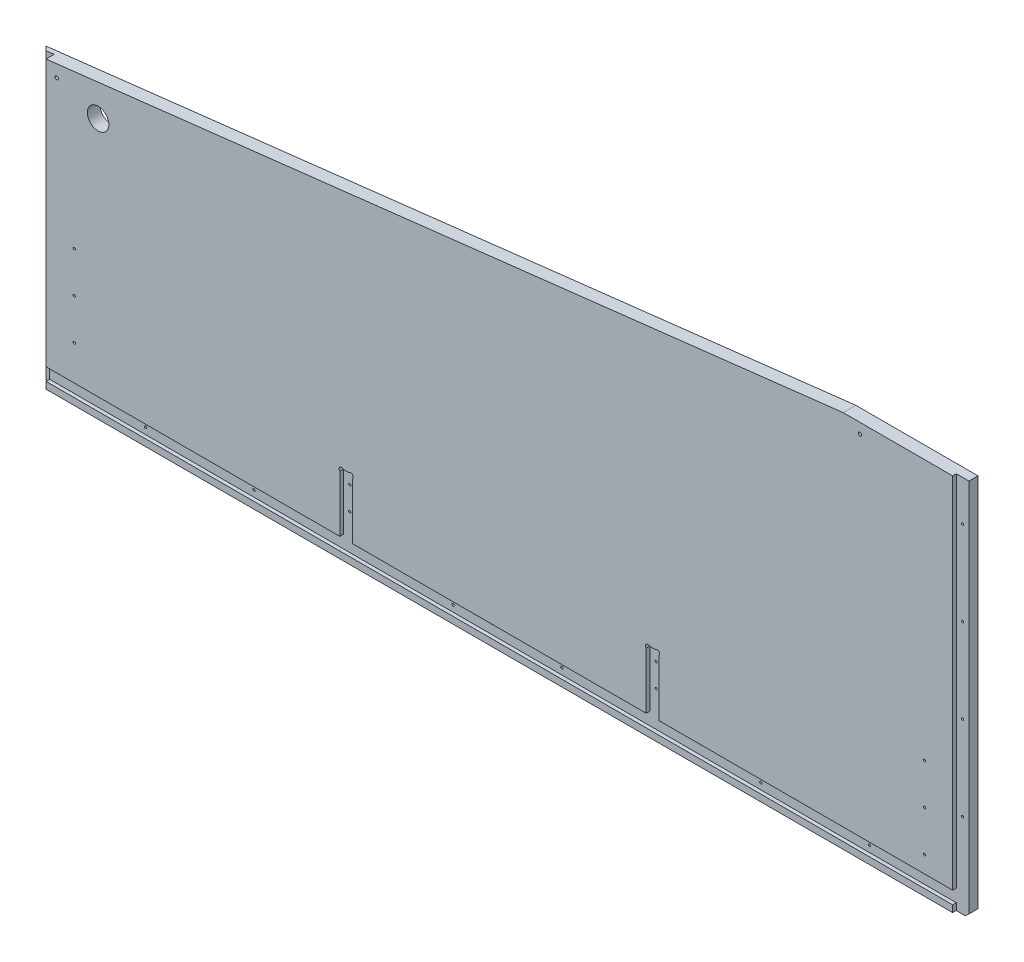
SolidWorks part; units mm, degrees
material "Pine"
ref_plane "Front Plane" through (0, 0, 0) normal (0, 0, 1) x (1, 0, 0)
ref_plane "Top Plane" through (0, 0, 0) normal (0, 1, 0) x (1, 0, 0)
ref_plane "Right Plane" through (0, 0, 0) normal (1, 0, 0) x (0, 0, -1)
sketch "Sketch1" plane through (0, 0, 0) normal (0, 0, 1) x (1, 0, 0)
  line L0 (8932.6508, -5243.5125) -> (10226.1458, -5243.5125)
  line L1 (9086.3208, -4722.0918) -> (10222.9708, -4853.7812)
  line L2 (8914.8708, -6342.0625) -> (10197.5708, -6342.0625)
  line L3 (8914.8708, -5808.6625) -> (10197.5708, -5808.6625)
  line L4 (8919.6333, -5253.0375) -> (10218.2083, -5253.0375)
  line L5 (9134.2633, -4656.1375) -> (9134.2633, -4638.3575)
  line L6 (9091.0833, -4638.3575) -> (9134.2633, -4638.3575)
  line L7 (9091.0833, -4567.2375) -> (9091.0833, -4638.3575)
  line L8 (9134.2633, -4656.1375) -> (9581.3033, -4656.1375)
  line L9 (9091.0833, -4567.2375) -> (9624.4833, -4567.2375)
  line L10 (9581.3033, -4656.1375) -> (9581.3033, -4638.3575)
  line L11 (9581.3033, -4638.3575) -> (9624.4833, -4638.3575)
  line L12 (9624.4833, -4567.2375) -> (9624.4833, -4638.3575)
  line L13 (8932.6508, -5225.7325) -> (9344.9775, -5225.7325)
  line L14 (8932.6508, -5256.2125) -> (8932.6508, -5243.5125)
  line L15 (8911.6958, -5256.2125) -> (8932.6508, -5256.2125)
  line L16 (8914.8708, -4722.0918) -> (9086.3208, -4722.0918)
  line L17 (8911.6958, -4715.5913) -> (8932.6508, -4715.5913)
  line L18 (8914.8708, -6342.0625) -> (8914.8708, -5808.6625)
  line L19 (12082.9917, -4722.0918) -> (10946.3417, -4853.7812)
  line L20 (12236.6617, -5243.5125) -> (10943.1667, -5243.5125)
  line L21 (10951.1042, -5253.0375) -> (12249.6792, -5253.0375)
  line L22 (10838.3917, -5656.2625) -> (11308.2917, -5656.2625)
  line L23 (10838.3917, -5719.7625) -> (11308.2917, -5719.7625)
  line L24 (10838.3917, -5742.5368) -> (11308.2917, -5742.5368)
  line L25 (10806.6417, -6342.0625) -> (11340.0417, -6342.0625)
  line L26 (10803.4667, -6335.7125) -> (11343.2167, -6335.7125)
  line L27 (10803.4667, -6317.9325) -> (11343.2167, -6317.9325)
  line L28 (10943.1667, -5225.7325) -> (11376.4483, -5225.7325)
  line L29 (11506.7292, -4754.5625) -> (10806.6417, -4827.5875)
  line L30 (11506.7292, -4567.2375) -> (11506.7292, -4754.5625)
  line L31 (10806.6417, -4567.2375) -> (10806.6417, -4827.5875)
  line L32 (10806.6417, -4567.2375) -> (11506.7292, -4567.2375)
  line L33 (10235.6708, -6329.3625) -> (10245.1958, -6329.3625)
  line L34 (10245.1958, -6329.3625) -> (10254.7208, -6278.5625)
  line L35 (10302.3458, -6329.3625) -> (10311.8708, -6278.5625)
  line L36 (10302.3458, -6329.3625) -> (10292.8208, -6329.3625)
  line L37 (10245.1958, -5821.3625) -> (10254.7208, -5872.1625)
  line L38 (10235.6708, -5821.3625) -> (10245.1958, -5821.3625)
  line L39 (10292.8208, -5821.3625) -> (10302.3458, -5821.3625)
  line L40 (10302.3458, -5821.3625) -> (10311.8708, -5872.1625)
  line L41 (10235.6708, -5821.3625) -> (10235.6708, -6329.3625)
  line L42 (10254.7208, -5872.1625) -> (10254.7208, -6278.5625)
  line L43 (10311.8708, -5872.1625) -> (10311.8708, -6278.5625)
  line L44 (10292.8208, -5821.3625) -> (10292.8208, -6329.3625)
  line L45 (8932.6508, -5225.7325) -> (8932.6508, -4715.5913)
  line L46 (8911.6958, -4715.5913) -> (8911.6958, -5256.2125)
  line L47 (8914.8708, -5248.275) -> (8914.8708, -4722.0918)
  line L48 (8919.6333, -5253.0375) -> (8914.8708, -5248.275)
  line L49 (8914.8708, -5145.0875) -> (8937.426, -5145.0875)
  line L50 (8914.8708, -5202.2375) -> (8937.426, -5202.2375)
  line L51 (10838.3917, -5656.2625) -> (10838.3917, -5719.7625)
  line L52 (10832.0417, -5736.1868) -> (10856.1717, -5736.1868)
  line L53 (10806.6417, -6342.0625) -> (10806.6417, -5818.7368)
  line L54 (10832.0417, -5649.9125) -> (10856.1717, -5649.9125)
  line L55 (10832.0417, -5726.1125) -> (10856.1717, -5726.1125)
  line L56 (10806.6417, -5818.7368) -> (10833.9015, -5818.7368)
  line L57 (10832.0417, -5806.0442) -> (10851.6815, -5806.0442)
  line L58 (10856.1717, -5801.5541) -> (10856.1717, -5736.1868)
  line L59 (10838.3917, -5814.2467) -> (10838.3917, -5742.5368)
  line L60 (10832.0417, -5806.0442) -> (10832.0417, -5736.1868)
  line L61 (10803.4667, -6317.9325) -> (10803.4667, -6335.7125)
  line L62 (10197.5708, -5808.6625) -> (10197.5708, -6342.0625)
  line L63 (9762.3842, -6348.4125) -> (9762.3842, -5802.3125)
  line L64 (9780.1642, -6348.4125) -> (9762.3842, -6348.4125)
  line L65 (9780.1642, -5802.3125) -> (9780.1642, -6348.4125)
  line L66 (9762.3842, -5802.3125) -> (9780.1642, -5802.3125)
  line L67 (9332.2775, -6348.4125) -> (9332.2775, -5802.3125)
  line L68 (9332.2775, -6348.4125) -> (9350.0575, -6348.4125)
  line L69 (9350.0575, -5802.3125) -> (9350.0575, -6348.4125)
  line L70 (9332.2775, -5802.3125) -> (9350.0575, -5802.3125)
  line L71 (9993.8374, -6061.075) -> (9993.8374, -6045.2418)
  line L72 (9998.5999, -6065.8375) -> (10014.4331, -6065.8375)
  line L73 (9998.5999, -6084.8875) -> (10014.4331, -6084.8875)
  line L74 (9993.8374, -6105.4832) -> (9993.8374, -6089.65)
  line L75 (9974.7874, -6105.4832) -> (9974.7874, -6089.65)
  line L76 (9954.1917, -6084.8875) -> (9970.0249, -6084.8875)
  line L77 (9974.7874, -6061.075) -> (9974.7874, -6045.2418)
  line L78 (9954.1917, -6065.8375) -> (9970.0249, -6065.8375)
  line L79 (10793.9417, -6237.2875) -> (10816.4969, -6237.2875)
  line L80 (10793.9417, -6294.4375) -> (10816.4969, -6294.4375)
  line L81 (10856.1717, -5649.9125) -> (10856.1717, -5726.1125)
  line L82 (10832.0417, -5726.1125) -> (10832.0417, -5649.9125)
  line L83 (10226.1458, -5225.7325) -> (10226.1458, -5243.5125)
  line L84 (10205.1908, -5257.8) -> (10205.1908, -4844.2499)
  line L85 (10230.9083, -4844.2499) -> (10230.9083, -5257.8)
  line L86 (10205.1908, -5257.8) -> (10230.9083, -5257.8)
  line L87 (10205.1908, -4844.2499) -> (10230.9083, -4844.2499)
  line L88 (10946.3417, -5176.8375) -> (10968.8969, -5176.8375)
  line L89 (9349.4676, -5141.9125) -> (9358.2674, -5141.9125)
  line L90 (10946.3417, -5119.6875) -> (10968.8969, -5119.6875)
  line L91 (9929.011, -4660.9635) -> (10066.0807, -4660.9635)
  line L92 (9929.011, -4678.7435) -> (10066.0807, -4678.7435)
  line L93 (10943.1667, -5225.7325) -> (10943.1667, -5243.5125)
  line L94 (10946.3417, -5248.275) -> (10951.1042, -5253.0375)
  line L95 (10946.3417, -5257.8063) -> (10946.3417, -4849.0188)
  line L96 (10964.1217, -5257.8) -> (10964.1217, -4844.2499)
  line L97 (10938.4042, -4844.2499) -> (10938.4042, -5257.8)
  line L98 (10938.4042, -5257.8) -> (10964.1217, -5257.8)
  line L99 (10964.1217, -4844.2499) -> (10938.4042, -4844.2499)
  line L100 (10344.8908, -4560.8875) -> (10369.0208, -4560.8875)
  line L101 (10344.8908, -4560.8875) -> (10369.0208, -4560.8875)
  line L102 (10800.2917, -4560.8875) -> (10824.4217, -4560.8875)
  line L103 (10200.4156, -5119.6875) -> (10222.9708, -5119.6875)
  line L104 (10200.4156, -5176.8375) -> (10222.9708, -5176.8375)
  line L105 (9344.9775, -5146.4026) -> (9344.9775, -5225.7325)
  line L106 (10344.8908, -4560.8875) -> (10344.8908, -4833.9375)
  line L107 (9792.8642, -5225.7325) -> (9792.8642, -5146.4026)
  line L108 (9362.7575, -5225.7325) -> (9775.0842, -5225.7325)
  line L109 (9680.3633, -4761.8396) -> (9680.3633, -4559.9604)
  line L110 (9656.2333, -4559.9604) -> (9680.3633, -4559.9604)
  line L111 (9656.2333, -4761.8396) -> (9680.3633, -4761.8396)
  line L112 (9656.2333, -4761.8396) -> (9656.2333, -4559.9604)
  line L113 (9779.5743, -5141.9125) -> (9788.374, -5141.9125)
  line L114 (10070.5708, -4665.4536) -> (10070.5708, -4674.2534)
  line L115 (9924.5208, -4674.2534) -> (9924.5208, -4665.4536)
  line L116 (12127.4417, -6188.3925) -> (12205.5015, -6188.3925)
  line L117 (12209.9917, -6170.6125) -> (12209.9917, -6183.9024)
  line L118 (9792.8642, -5225.7325) -> (10226.1458, -5225.7325)
  line L119 (9662.5833, -4754.5625) -> (10362.6708, -4827.5875)
  line L120 (9662.5833, -4567.2375) -> (9662.5833, -4754.5625)
  line L121 (10362.6708, -4567.2375) -> (10362.6708, -4827.5875)
  line L122 (9662.5833, -4567.2375) -> (10362.6708, -4567.2375)
  line L123 (10824.4217, -4833.9375) -> (10800.2917, -4833.9375)
  line L124 (10800.2917, -4833.9375) -> (10800.2917, -4560.8875)
  line L125 (10824.4217, -4560.8875) -> (10824.4217, -4833.9375)
  line L126 (10344.8908, -4833.9375) -> (10369.0208, -4833.9375)
  line L127 (10369.0208, -4833.9375) -> (10369.0208, -4560.8875)
  line L128 (10222.9708, -5248.275) -> (10218.2083, -5253.0375)
  line L129 (10222.9708, -5257.8063) -> (10222.9708, -4849.0188)
  line L130 (11734.6544, -5701.375) -> (11739.2301, -5701.375)
  line L131 (9362.7575, -5225.7325) -> (9362.7575, -5146.4026)
  line L132 (9775.0842, -5146.4026) -> (9775.0842, -5225.7325)
  line L133 (11761.3864, -5701.375) -> (11756.8282, -5701.375)
  line L134 (11734.6544, -5693.755) -> (11739.2301, -5693.755)
  line L135 (11761.4039, -5693.755) -> (11756.8282, -5693.755)
  line L136 (11734.6544, -5701.375) -> (11739.2301, -5701.375)
  line L137 (11744.3462, -5721.3024) -> (11744.3462, -5706.4179)
  line L138 (11751.7122, -5721.3024) -> (11751.7122, -5706.4179)
  line L139 (11740.0917, -6170.6125) -> (11740.0917, -6183.9024)
  line L140 (11689.2917, -6188.3925) -> (11822.6417, -6188.3925)
  line L141 (11689.2917, -6348.4093) -> (11689.2917, -6164.2657)
  line L142 (11689.2917, -6164.2657) -> (11746.4417, -6164.2657)
  line L143 (11746.4417, -6164.2657) -> (11746.4417, -6188.3925)
  line L144 (11689.2917, -6164.2657) -> (11746.4417, -6164.2657)
  line L145 (11340.0417, -5818.7368) -> (11340.0417, -6342.0625)
  line L146 (11290.5117, -5726.1125) -> (11314.6417, -5726.1125)
  line L147 (11290.5117, -5649.9125) -> (11290.5117, -5726.1125)
  line L148 (11340.0417, -5818.7368) -> (11312.7818, -5818.7368)
  line L149 (11314.6417, -5806.0442) -> (11295.0018, -5806.0442)
  line L150 (11290.5117, -5801.5541) -> (11290.5117, -5736.1868)
  line L151 (11308.2917, -5814.2467) -> (11308.2917, -5742.5368)
  line L152 (11314.6417, -5806.0442) -> (11314.6417, -5736.1868)
  line L153 (11290.5117, -5736.1868) -> (11314.6417, -5736.1868)
  line L154 (11848.0417, -6267.1325) -> (11962.3417, -6267.1325)
  line L155 (11962.3417, -6267.1325) -> (11962.3417, -6203.6325)
  line L156 (11343.2167, -6317.9325) -> (11343.2167, -6335.7125)
  line L157 (11365.4417, -5656.2625) -> (11365.4417, -5719.7625)
  line L158 (11365.4417, -5656.2625) -> (11479.7417, -5656.2625)
  line L159 (11778.1917, -6071.3937) -> (11802.3217, -6071.3937)
  line L160 (11314.6417, -5726.1125) -> (11314.6417, -5649.9125)
  line L161 (11314.6417, -5649.9125) -> (11290.5117, -5649.9125)
  line L162 (11308.2917, -5719.7625) -> (11308.2917, -5656.2625)
  line L163 (11689.2917, -6348.4093) -> (11713.4217, -6348.4093)
  line L164 (12203.6417, -6164.2657) -> (12260.7917, -6164.2657)
  line L165 (11713.4217, -6348.4093) -> (11713.4217, -6164.2657)
  line L166 (11695.6417, -6342.0625) -> (11695.6417, -6170.6125)
  line L167 (11695.6417, -6048.5337) -> (11699.4517, -6052.3437)
  line L168 (11822.6417, -6292.5325) -> (11822.6417, -6188.3925)
  line L169 (11695.6417, -6342.0625) -> (11695.6417, -6170.6125)
  line L170 (11848.0417, -6203.6325) -> (11962.3417, -6203.6325)
  line L171 (11848.0417, -6203.6325) -> (11848.0417, -6267.1325)
  line L172 (11987.7417, -6267.1325) -> (11987.7417, -6203.6325)
  line L173 (11784.5417, -6077.7437) -> (11784.5417, -6141.2438)
  line L174 (11517.8417, -5656.2625) -> (11632.1417, -5656.2625)
  line L175 (11632.1417, -5656.2625) -> (11632.1417, -5719.7625)
  line L176 (11632.1417, -5719.7625) -> (11517.8417, -5719.7625)
  line L177 (11517.8417, -5719.7625) -> (11517.8417, -5656.2625)
  line L178 (11692.4667, -6028.2137) -> (11692.4667, -6045.9937)
  line L179 (11695.6417, -5979.3188) -> (11718.1969, -5979.3188)
  line L180 (11695.6417, -5922.1687) -> (11718.1969, -5922.1687)
  line L181 (11821.0415, -5722.9375) -> (11821.0415, -5943.6)
  line L182 (11687.7042, -5651.5) -> (11701.9917, -5651.5)
  line L183 (11687.7042, -5651.5) -> (11687.7042, -6055.5251)
  line L184 (11687.7042, -6055.5251) -> (11701.9917, -6055.5251)
  line L185 (11701.9917, -6055.5251) -> (11701.9917, -5651.5)
  line L186 (11695.6417, -6055.2013) -> (11695.6417, -5649.595)
  line L187 (11695.6417, -5656.2625) -> (11695.6417, -6048.5337)
  line L188 (11695.6417, -6170.6125) -> (11740.0917, -6170.6125)
  line L189 (12203.6417, -6164.2657) -> (12203.6417, -6188.3925)
  line L190 (12254.4417, -6342.0625) -> (12254.4417, -6170.6125)
  line L191 (12129.0419, -5943.6) -> (12129.0419, -5722.9375)
  line L192 (12254.4417, -6048.5337) -> (12250.6317, -6052.3437)
  line L193 (12257.6167, -6045.9937) -> (12257.6167, -6028.2137)
  line L194 (12248.0917, -5651.5) -> (12262.3792, -5651.5)
  line L195 (12262.3792, -5651.5) -> (12262.3792, -6055.5251)
  line L196 (12262.3792, -6055.5251) -> (12248.0917, -6055.5251)
  line L197 (12248.0917, -6055.5251) -> (12248.0917, -5651.5)
  line L198 (12254.4417, -6141.2438) -> (12254.4417, -6077.7437)
  line L199 (12236.6617, -6164.2657) -> (12260.7917, -6164.2657)
  line L200 (12102.0417, -6267.1325) -> (11987.7417, -6267.1325)
  line L201 (11330.1865, -6237.2875) -> (11352.7417, -6237.2875)
  line L202 (11330.1865, -6294.4375) -> (11352.7417, -6294.4375)
  line L203 (11474.6617, -5851.8425) -> (11492.4417, -5851.8425)
  line L204 (11474.6617, -5808.6625) -> (11474.6617, -5851.8425)
  line L205 (11403.5417, -5808.6625) -> (11474.6617, -5808.6625)
  line L206 (11492.4417, -5851.8425) -> (11492.4417, -6298.8825)
  line L207 (11403.5417, -6342.0625) -> (11403.5417, -5808.6625)
  line L208 (11474.6617, -6298.8825) -> (11492.4417, -6298.8825)
  line L209 (11474.6617, -6342.0625) -> (11474.6617, -6298.8825)
  line L210 (11403.5417, -6342.0625) -> (11474.6617, -6342.0625)
  line L211 (11619.4417, -5851.8425) -> (11601.6617, -5851.8425)
  line L212 (11601.6617, -5808.6625) -> (11601.6617, -5851.8425)
  line L213 (11530.5417, -5808.6625) -> (11601.6617, -5808.6625)
  line L214 (11619.4417, -5851.8425) -> (11619.4417, -6298.8825)
  line L215 (11530.5417, -6342.0625) -> (11530.5417, -5808.6625)
  line L216 (11619.4417, -6298.8825) -> (11601.6617, -6298.8825)
  line L217 (11601.6617, -6342.0625) -> (11601.6617, -6298.8825)
  line L218 (11530.5417, -6342.0625) -> (11601.6617, -6342.0625)
  line L219 (11479.7417, -5719.7625) -> (11479.7417, -5656.2625)
  line L220 (11365.4417, -5719.7625) -> (11479.7417, -5719.7625)
  line L221 (11778.1917, -6147.5937) -> (11802.3217, -6147.5937)
  line L222 (11802.3217, -6071.3937) -> (11802.3217, -6147.5937)
  line L223 (11778.1917, -6147.5937) -> (11778.1917, -6071.3937)
  line L224 (12254.4417, -5922.1687) -> (12231.8865, -5922.1687)
  line L225 (12254.4417, -5979.3188) -> (12231.8865, -5979.3188)
  line L226 (12254.4417, -6055.2013) -> (12254.4417, -5649.595)
  line L227 (12254.4417, -6048.5337) -> (12254.4417, -5656.2625)
  line L228 (11841.6917, -5702.2873) -> (12108.3917, -5702.2873)
  line L229 (11822.6417, -6292.5325) -> (12127.4417, -6292.5325)
  line L230 (12127.4417, -6292.5325) -> (12127.4417, -6188.3925)
  line L231 (12254.4417, -6170.6125) -> (12209.9917, -6170.6125)
  line L232 (11695.6417, -6342.0625) -> (12254.4417, -6342.0625)
  line L233 (12236.6617, -6348.4093) -> (12260.7917, -6348.4093)
  line L234 (12260.7917, -6348.4093) -> (12260.7917, -6164.2657)
  line L235 (12236.6617, -6348.4093) -> (12236.6617, -6164.2657)
  line L236 (12102.0417, -6203.6325) -> (12102.0417, -6267.1325)
  line L237 (11987.7417, -6203.6325) -> (12102.0417, -6203.6325)
  line L238 (12236.6617, -6147.5937) -> (12236.6617, -6071.3937)
  line L239 (12203.6417, -6188.3925) -> (12260.7917, -6188.3925)
  line L240 (11098.7417, -4665.4536) -> (11098.7417, -4674.2534)
  line L241 (11394.2283, -5146.4026) -> (11394.2283, -5225.7325)
  line L242 (11376.4483, -5225.7325) -> (11376.4483, -5146.4026)
  line L243 (11394.2283, -5225.7325) -> (11806.555, -5225.7325)
  line L244 (11841.6917, -5964.2502) -> (12108.3917, -5964.2502)
  line L245 (12236.6617, -6147.5937) -> (12260.7917, -6147.5937)
  line L246 (12236.6617, -5256.2125) -> (12236.6617, -5243.5125)
  line L247 (12260.7917, -6147.5937) -> (12260.7917, -6071.3937)
  line L248 (12260.7917, -6071.3937) -> (12236.6617, -6071.3937)
  line L249 (12254.4417, -6077.7437) -> (11784.5417, -6077.7437)
  line L250 (11784.5417, -6141.2438) -> (12254.4417, -6141.2438)
  line L252 (12254.4417, -5656.2625) -> (11695.6417, -5656.2625)
  line L253 (11699.4517, -6052.3437) -> (12250.6317, -6052.3437)
  line L254 (11692.4667, -6045.9937) -> (12257.6167, -6045.9937)
  line L255 (11692.4667, -6028.2137) -> (12257.6167, -6028.2137)
  line L256 (11824.335, -5146.4026) -> (11824.335, -5225.7325)
  line L257 (11811.0451, -5141.9125) -> (11819.8449, -5141.9125)
  line L258 (11244.7917, -4674.2534) -> (11244.7917, -4665.4536)
  line L259 (11806.555, -5225.7325) -> (11806.555, -5146.4026)
  line L260 (11488.9492, -4761.8396) -> (11488.9492, -4559.9604)
  line L261 (11488.9492, -4559.9604) -> (11513.0792, -4559.9604)
  line L262 (11488.9492, -4761.8396) -> (11513.0792, -4761.8396)
  line L263 (11513.0792, -4761.8396) -> (11513.0792, -4559.9604)
  line L264 (11240.3015, -4660.9635) -> (11103.2318, -4660.9635)
  line L265 (11103.2318, -4678.7435) -> (11240.3015, -4678.7435)
  line L266 (12236.6617, -5225.7325) -> (12236.6617, -4715.5913)
  line L267 (12257.6167, -4715.5913) -> (12257.6167, -5256.2125)
  line L268 (12254.4417, -5248.275) -> (12254.4417, -4722.0918)
  line L269 (12236.6617, -5225.7325) -> (11824.335, -5225.7325)
  line L270 (12035.0492, -4656.1375) -> (12035.0492, -4638.3575)
  line L271 (12078.2292, -4638.3575) -> (12035.0492, -4638.3575)
  line L272 (12078.2292, -4567.2375) -> (12078.2292, -4638.3575)
  line L273 (12035.0492, -4656.1375) -> (11588.0092, -4656.1375)
  line L274 (11544.8292, -4567.2375) -> (12078.2292, -4567.2375)
  line L275 (11588.0092, -4656.1375) -> (11588.0092, -4638.3575)
  line L276 (11544.8292, -4638.3575) -> (11588.0092, -4638.3575)
  line L277 (11544.8292, -4567.2375) -> (11544.8292, -4638.3575)
  line L278 (12249.6792, -5253.0375) -> (12254.4417, -5248.275)
  line L280 (12257.6167, -5256.2125) -> (12236.6617, -5256.2125)
  line L281 (12231.8865, -5145.0875) -> (12254.4417, -5145.0875)
  line L282 (12231.8865, -5202.2375) -> (12254.4417, -5202.2375)
  line L283 (12236.6617, -4715.5913) -> (12257.6167, -4715.5913)
  line L284 (12082.9917, -4722.0918) -> (12254.4417, -4722.0918)
  line L285 (11380.9385, -5141.9125) -> (11389.7382, -5141.9125)
  circle A0 centre (8923.7608, -4778.9042) radius 1.5875
  circle A1 centre (9062.6598, -4736.3765) radius 2.3685
  circle A2 centre (9051.3958, -6281.7375) radius 22.225
  circle A3 centre (9083.1458, -6249.9875) radius 1.5875
  circle A4 centre (9083.1458, -6313.4875) radius 1.5875
  circle A5 centre (9019.6458, -6249.9875) radius 1.5875
  circle A6 centre (9019.6458, -6313.4875) radius 1.5875
  circle A7 centre (8972.3383, -5202.2375) radius 1.5875
  circle A8 centre (8923.7608, -5015.9708) radius 1.5875
  circle A9 centre (8923.7608, -5134.5042) radius 1.5875
  circle A10 centre (9054.5708, -5234.6225) radius 1.5875
  circle A11 centre (8923.7608, -4897.4375) radius 1.5875
  circle A12 centre (8972.3383, -5087.9375) radius 1.5875
  circle A13 centre (8972.3383, -5145.0875) radius 1.5875
  circle A14 centre (10847.2817, -5668.9625) radius 1.5875
  circle A15 centre (10847.2817, -5707.0625) radius 1.5875
  circle A16 centre (10847.2817, -5755.2368) radius 1.5875
  circle A17 centre (10851.4092, -6237.2875) radius 1.5875
  circle A18 centre (10851.4092, -6294.4375) radius 1.5875
  circle A19 centre (10847.2817, -5793.3442) radius 1.5875
  arc A20 (10833.9015, -5818.7368) -> (10838.3917, -5814.2467) centre (10836.1466, -5816.4918) ccw
  arc A21 (10851.6815, -5806.0442) -> (10856.1717, -5801.5541) centre (10853.9266, -5803.7992) ccw
  circle A22 centre (10882.8417, -6040.4375) radius 1.5875
  circle A23 centre (10882.8417, -6218.2375) radius 1.5875
  circle A24 centre (10882.8417, -5862.6375) radius 1.5875
  circle A25 centre (10908.2417, -6326.8225) radius 1.5875
  circle A26 centre (10908.2417, -6326.8225) radius 1.5875
  circle A27 centre (10851.4092, -6180.1375) radius 1.5875
  circle A28 centre (10815.5317, -4783.4231) radius 1.5875
  circle A29 centre (10815.5317, -4696.9488) radius 1.5875
  circle A30 centre (10815.5317, -4610.4746) radius 1.5875
  circle A31 centre (10979.1323, -4867.0082) radius 2.3685
  circle A32 centre (10190.1802, -4867.0082) radius 2.3685
  circle A33 centre (10955.2317, -4929.9812) radius 1.5875
  circle A34 centre (10955.2317, -5031.5812) radius 1.5875
  circle A35 centre (10214.0808, -4929.9812) radius 1.5875
  circle A36 centre (10214.0808, -5031.5812) radius 1.5875
  circle A37 centre (9341.1675, -6265.8625) radius 1.5875
  circle A38 centre (9771.2742, -5884.8625) radius 1.5875
  circle A39 centre (9771.2742, -6138.8625) radius 1.5875
  circle A40 centre (9771.2742, -6011.8625) radius 1.5875
  arc A41 (10036.2287, -6113.8083) -> (10051.3426, -6111.6033) centre (10042.9639, -6107.0732) ccw
  arc A42 (10051.3426, -6111.6033) -> (10051.3426, -6039.1217) centre (9984.3124, -6075.3625) ccw
  arc A43 (10051.3426, -6039.1217) -> (10036.2287, -6036.9167) centre (10042.9639, -6043.6518) ccw
  arc A44 (10034.5851, -6102.5431) -> (10034.5851, -6048.1819) centre (9984.3124, -6075.3625) ccw
  arc A45 (10034.5851, -6102.5431) -> (10036.2287, -6113.8083) centre (10042.9639, -6107.0732) ccw
  arc A46 (10036.2287, -6036.9167) -> (10034.5851, -6048.1819) centre (10042.9639, -6043.6518) ccw
  arc A47 (9945.8666, -6127.2787) -> (9948.0717, -6142.3927) centre (9952.6018, -6134.0139) ccw
  arc A48 (9948.0717, -6142.3927) -> (10020.5532, -6142.3927) centre (9984.3124, -6075.3625) ccw
  arc A49 (10020.5532, -6142.3927) -> (10022.7583, -6127.2787) centre (10016.0231, -6134.0139) ccw
  arc A50 (9957.1319, -6125.6352) -> (10011.493, -6125.6352) centre (9984.3124, -6075.3625) ccw
  arc A51 (9957.1319, -6125.6352) -> (9945.8666, -6127.2787) centre (9952.6018, -6134.0139) ccw
  arc A52 (10022.7583, -6127.2787) -> (10011.493, -6125.6352) centre (10016.0231, -6134.0139) ccw
  arc A53 (9932.3962, -6036.9167) -> (9917.2822, -6039.1217) centre (9925.661, -6043.6518) ccw
  arc A54 (9917.2822, -6039.1217) -> (9917.2822, -6111.6033) centre (9984.3124, -6075.3625) ccw
  arc A55 (9917.2822, -6111.6033) -> (9932.3962, -6113.8083) centre (9925.661, -6107.0732) ccw
  arc A56 (9934.0398, -6048.1819) -> (9934.0398, -6102.5431) centre (9984.3124, -6075.3625) ccw
  arc A57 (9934.0398, -6048.1819) -> (9932.3962, -6036.9167) centre (9925.661, -6043.6518) ccw
  arc A58 (9932.3962, -6113.8083) -> (9934.0398, -6102.5431) centre (9925.661, -6107.0732) ccw
  arc A59 (9945.8666, -6023.4463) -> (9957.1319, -6025.0898) centre (9952.6018, -6016.7111) ccw
  arc A60 (10011.493, -6025.0898) -> (10022.7583, -6023.4463) centre (10016.0231, -6016.7111) ccw
  arc A61 (10011.493, -6025.0898) -> (9957.1319, -6025.0898) centre (9984.3124, -6075.3625) ccw
  arc A62 (9948.0717, -6008.3323) -> (9945.8666, -6023.4463) centre (9952.6018, -6016.7111) ccw
  arc A63 (10020.5532, -6008.3323) -> (9948.0717, -6008.3323) centre (9984.3124, -6075.3625) ccw
  arc A64 (10022.7583, -6023.4463) -> (10020.5532, -6008.3323) centre (10016.0231, -6016.7111) ccw
  arc A65 (10005.0943, -6187.7574) -> (10096.7073, -6096.1443) centre (9984.3124, -6075.3625) ccw
  arc A66 (9993.8374, -6178.3911) -> (10005.0943, -6187.7574) centre (10003.3624, -6178.3911) ccw
  arc A67 (10001.6306, -6169.0249) -> (10077.9748, -6092.6807) centre (9984.3124, -6075.3625) ccw
  arc A68 (10087.3411, -6084.8875) -> (10077.9748, -6092.6807) centre (10087.3411, -6094.4125) ccw
  arc A69 (10001.6306, -6169.0249) -> (9993.8374, -6178.3911) centre (10003.3624, -6178.3911) ccw
  arc A70 (9963.5306, -6187.7574) -> (9974.7874, -6178.3911) centre (9965.2624, -6178.3911) ccw
  arc A71 (9871.9176, -6096.1443) -> (9963.5306, -6187.7574) centre (9984.3124, -6075.3625) ccw
  arc A72 (9881.2838, -6084.8875) -> (9871.9176, -6096.1443) centre (9881.2838, -6094.4125) ccw
  arc A73 (9890.65, -6092.6807) -> (9966.9943, -6169.0249) centre (9984.3124, -6075.3625) ccw
  arc A74 (9974.7874, -6178.3911) -> (9966.9943, -6169.0249) centre (9965.2624, -6178.3911) ccw
  arc A75 (9890.65, -6092.6807) -> (9881.2838, -6084.8875) centre (9881.2838, -6094.4125) ccw
  arc A76 (9871.9176, -6054.5807) -> (9881.2838, -6065.8375) centre (9881.2838, -6056.3125) ccw
  arc A77 (9963.5306, -5962.9676) -> (9871.9176, -6054.5807) centre (9984.3124, -6075.3625) ccw
  arc A78 (9974.7874, -5972.3339) -> (9963.5306, -5962.9676) centre (9965.2624, -5972.3339) ccw
  arc A79 (9966.9943, -5981.7001) -> (9890.65, -6058.0443) centre (9984.3124, -6075.3625) ccw
  arc A80 (9881.2838, -6065.8375) -> (9890.65, -6058.0443) centre (9881.2838, -6056.3125) ccw
  arc A81 (9966.9943, -5981.7001) -> (9974.7874, -5972.3339) centre (9965.2624, -5972.3339) ccw
  arc A82 (10077.9748, -6058.0443) -> (10087.3411, -6065.8375) centre (10087.3411, -6056.3125) ccw
  arc A83 (9993.8374, -5972.3339) -> (10001.6306, -5981.7001) centre (10003.3624, -5972.3339) ccw
  arc A84 (10077.9748, -6058.0443) -> (10001.6306, -5981.7001) centre (9984.3124, -6075.3625) ccw
  arc A85 (10087.3411, -6065.8375) -> (10096.7073, -6054.5807) centre (10087.3411, -6056.3125) ccw
  arc A86 (10096.7073, -6054.5807) -> (10005.0943, -5962.9676) centre (9984.3124, -6075.3625) ccw
  arc A87 (10005.0943, -5962.9676) -> (9993.8374, -5972.3339) centre (10003.3624, -5972.3339) ccw
  arc A88 (10014.4331, -6065.8375) -> (10018.7361, -6059.0339) centre (10014.4331, -6061.075) ccw
  arc A89 (10018.7361, -6059.0339) -> (10000.641, -6040.9388) centre (9984.3124, -6075.3625) ccw
  arc A90 (10000.641, -6040.9388) -> (9993.8374, -6045.2418) centre (9998.5999, -6045.2418) ccw
  arc A91 (9993.8374, -6061.075) -> (9998.5999, -6065.8375) centre (9998.5999, -6061.075) ccw
  arc A92 (9993.8374, -6105.4832) -> (10000.641, -6109.7862) centre (9998.5999, -6105.4832) ccw
  arc A93 (10000.641, -6109.7862) -> (10018.7361, -6091.6911) centre (9984.3124, -6075.3625) ccw
  arc A94 (10018.7361, -6091.6911) -> (10014.4331, -6084.8875) centre (10014.4331, -6089.65) ccw
  arc A95 (9998.5999, -6084.8875) -> (9993.8374, -6089.65) centre (9998.5999, -6089.65) ccw
  arc A96 (9954.1917, -6084.8875) -> (9949.8888, -6091.6911) centre (9954.1917, -6089.65) ccw
  arc A97 (9949.8888, -6091.6911) -> (9967.9839, -6109.7862) centre (9984.3124, -6075.3625) ccw
  arc A98 (9967.9839, -6109.7862) -> (9974.7874, -6105.4832) centre (9970.0249, -6105.4832) ccw
  arc A99 (9974.7874, -6089.65) -> (9970.0249, -6084.8875) centre (9970.0249, -6089.65) ccw
  arc A100 (9970.0249, -6065.8375) -> (9974.7874, -6061.075) centre (9970.0249, -6061.075) ccw
  arc A101 (9949.8888, -6059.0339) -> (9954.1917, -6065.8375) centre (9954.1917, -6061.075) ccw
  arc A102 (9967.9839, -6040.9388) -> (9949.8888, -6059.0339) centre (9984.3124, -6075.3625) ccw
  arc A103 (9974.7874, -6045.2418) -> (9967.9839, -6040.9388) centre (9970.0249, -6045.2418) ccw
  arc A104 (10096.7073, -6096.1443) -> (10087.3411, -6084.8875) centre (10087.3411, -6094.4125) ccw
  circle A105 centre (9771.2742, -6265.8625) radius 1.5875
  circle A106 centre (9341.1675, -5884.8625) radius 1.5875
  circle A107 centre (9341.1675, -6138.8625) radius 1.5875
  circle A108 centre (9341.1675, -6011.8625) radius 1.5875
  circle A109 centre (11037.2315, -4887.5494) radius 15.0812
  arc A110 (9349.4676, -5141.9125) -> (9344.9775, -5146.4026) centre (9347.2226, -5144.1576) ccw
  arc A111 (9362.7575, -5146.4026) -> (9358.2674, -5141.9125) centre (9360.5124, -5144.1576) ccw
  circle A112 centre (9946.7458, -4669.8535) radius 1.5875
  arc A113 (9924.5208, -4674.2534) -> (9929.011, -4678.7435) centre (9926.7659, -4676.4984) ccw
  circle A114 centre (11003.8092, -5176.8375) radius 1.5875
  circle A115 centre (11003.8092, -5119.6875) radius 1.5875
  circle A116 centre (10353.7808, -4696.9488) radius 1.5875
  circle A117 centre (10353.7808, -4610.4746) radius 1.5875
  circle A118 centre (10353.7808, -4783.4231) radius 1.5875
  circle A119 centre (11003.8092, -5062.5375) radius 1.5875
  circle A120 centre (9353.8675, -5160.9625) radius 1.5875
  circle A121 centre (9638.7708, -5234.6225) radius 1.5875
  circle A122 centre (9671.4733, -4724.1144) radius 1.5875
  circle A123 centre (9671.4733, -4661.3637) radius 1.5875
  circle A124 centre (9671.4733, -4598.6129) radius 1.5875
  arc A125 (9792.8642, -5146.4026) -> (9788.374, -5141.9125) centre (9790.6191, -5144.1576) ccw
  arc A126 (9779.5743, -5141.9125) -> (9775.0842, -5146.4026) centre (9777.3292, -5144.1576) ccw
  circle A127 centre (10048.3458, -4669.8535) radius 1.5875
  arc A128 (10070.5708, -4665.4536) -> (10066.0807, -4660.9635) centre (10068.3258, -4663.2086) ccw
  arc A129 (10066.0807, -4678.7435) -> (10070.5708, -4674.2534) centre (10068.3258, -4676.4984) ccw
  circle A130 centre (9997.5458, -4669.8535) radius 1.5875
  arc A131 (9929.011, -4660.9635) -> (9924.5208, -4665.4536) centre (9926.7659, -4663.2086) ccw
  circle A132 centre (10132.081, -4887.5494) radius 15.0812
  circle A133 centre (10165.5033, -5176.8375) radius 1.5875
  circle A134 centre (10165.5033, -5119.6875) radius 1.5875
  circle A135 centre (9486.3708, -5234.6225) radius 1.5875
  circle A136 centre (10165.5033, -5062.5375) radius 1.5875
  circle A137 centre (9206.9708, -5234.6225) radius 1.5875
  circle A138 centre (10070.5708, -5234.6225) radius 1.5875
  circle A139 centre (9918.1708, -5234.6225) radius 1.5875
  circle A140 centre (9783.9742, -5160.9625) radius 1.5875
  circle A141 centre (9783.9742, -5193.9825) radius 1.5875
  circle A142 centre (9353.8675, -5193.9825) radius 1.5875
  circle A143 centre (11073.3417, -6326.8225) radius 1.5875
  circle A144 centre (11073.3417, -6326.8225) radius 1.5875
  circle A145 centre (11295.2742, -6180.1375) radius 1.5875
  circle A146 centre (11295.2742, -6294.4375) radius 1.5875
  circle A147 centre (11295.2742, -6237.2875) radius 1.5875
  circle A148 centre (11975.0417, -5692.775) radius 3.4925
  circle A149 centre (11263.8417, -5862.6375) radius 1.5875
  arc A150 (11739.2301, -5701.375) -> (11744.3462, -5706.4179) centre (11748.0292, -5697.565) ccw
  arc A151 (11751.7122, -5706.4179) -> (11756.8282, -5701.375) centre (11748.0292, -5697.565) ccw
  arc A152 (11744.3462, -5721.3024) -> (11751.7122, -5721.3024) centre (11748.0292, -5725.505) ccw
  arc A153 (11734.6544, -5693.755) -> (11724.9787, -5697.565) centre (11730.5667, -5697.565) ccw
  arc A154 (11756.8282, -5693.755) -> (11739.2301, -5693.755) centre (11748.0292, -5697.565) ccw
  arc A155 (11724.9787, -5697.565) -> (11734.6544, -5701.375) centre (11730.5667, -5697.565) ccw
  arc A156 (11761.3864, -5701.375) -> (11771.0797, -5697.565) centre (11765.4842, -5697.565) ccw
  arc A157 (11771.0797, -5697.565) -> (11761.4039, -5693.755) centre (11765.4917, -5697.565) ccw
  arc A158 (11740.0917, -6183.9024) -> (11744.5818, -6188.3925) centre (11742.3367, -6186.1474) ccw
  arc A159 (12205.5015, -6188.3925) -> (12209.9917, -6183.9024) centre (12207.7466, -6186.1474) ccw
  circle A160 centre (11299.4017, -5793.3442) radius 1.5875
  arc A161 (11308.2917, -5814.2467) -> (11312.7818, -5818.7368) centre (11310.5367, -5816.4918) ccw
  arc A162 (11290.5117, -5801.5541) -> (11295.0018, -5806.0442) centre (11292.7567, -5803.7992) ccw
  circle A163 centre (11704.5317, -6314.149) radius 1.5875
  circle A164 centre (11748.9817, -6208.7125) radius 1.5875
  circle A165 centre (11263.8417, -6218.2375) radius 1.5875
  circle A166 centre (11263.8417, -6040.4375) radius 1.5875
  circle A167 centre (11238.4417, -6326.8225) radius 1.5875
  circle A168 centre (11238.4417, -6326.8225) radius 1.5875
  circle A169 centre (11299.4017, -5668.9625) radius 1.5875
  circle A170 centre (11299.4017, -5707.0625) radius 1.5875
  circle A171 centre (11726.7567, -6179.5025) radius 1.5875
  circle A172 centre (11704.5317, -6199.3198) radius 1.5875
  circle A173 centre (11748.9817, -6272.2125) radius 1.5875
  circle A174 centre (11704.5317, -6256.7344) radius 1.5875
  circle A175 centre (11299.4017, -5755.2368) radius 1.5875
  circle A176 centre (11913.4467, -6301.4225) radius 1.5875
  circle A177 centre (11790.2567, -6301.4225) radius 1.5875
  circle A178 centre (11793.4317, -6128.5437) radius 1.5875
  circle A179 centre (11753.1092, -5865.0188) radius 1.5875
  circle A180 centre (11809.9417, -6037.1038) radius 1.5875
  circle A181 centre (11809.9417, -6037.1038) radius 1.5875
  circle A182 centre (11753.1092, -5922.1687) radius 1.5875
  circle A183 centre (11975.0417, -5973.7625) radius 3.4925
  circle A184 centre (11975.0417, -6037.1038) radius 1.5875
  circle A185 centre (11753.1092, -5979.3188) radius 1.5875
  circle A186 centre (11975.0417, -6037.1038) radius 1.5875
  arc A187 (11841.6917, -5702.2873) -> (11821.0415, -5722.9375) centre (11841.6917, -5722.9375) ccw
  circle A188 centre (11811.5292, -5833.2687) radius 3.4925
  arc A189 (11821.0415, -5943.6) -> (11841.6917, -5964.2502) centre (11841.6917, -5943.6) ccw
  circle A190 centre (12196.9742, -5865.0188) radius 1.5875
  arc A191 (12129.0419, -5722.9375) -> (12108.3917, -5702.2873) centre (12108.3917, -5722.9375) ccw
  circle A192 centre (12036.6367, -6301.4225) radius 1.5875
  circle A193 centre (12159.8267, -6301.4225) radius 1.5875
  circle A194 centre (12138.5542, -5833.2687) radius 3.4925
  circle A195 centre (12197.2917, -5761.0375) radius 15.0812
  circle A196 centre (11793.4317, -6090.4437) radius 1.5875
  circle A197 centre (12196.9742, -5922.1687) radius 1.5875
  arc A198 (12108.3917, -5964.2502) -> (12129.0419, -5943.6) centre (12108.3917, -5943.6) ccw
  circle A199 centre (12196.9742, -5979.3188) radius 1.5875
  circle A200 centre (12201.1017, -6272.2125) radius 1.5875
  circle A201 centre (12245.5517, -6314.149) radius 1.5875
  circle A202 centre (12245.5517, -6256.7344) radius 1.5875
  circle A203 centre (12201.1017, -6208.7125) radius 1.5875
  circle A204 centre (12223.3267, -6179.5025) radius 1.5875
  circle A205 centre (12245.5517, -6199.3198) radius 1.5875
  circle A206 centre (11171.7667, -4669.8535) radius 1.5875
  circle A207 centre (11222.5667, -4669.8535) radius 1.5875
  arc A208 (11240.3015, -4678.7435) -> (11244.7917, -4674.2534) centre (11242.5466, -4676.4984) ccw
  circle A209 centre (11385.3383, -5193.9825) radius 1.5875
  circle A210 centre (12106.6527, -4736.3765) radius 2.3685
  circle A211 centre (12140.1417, -6037.1038) radius 1.5875
  circle A212 centre (12140.1417, -6037.1038) radius 1.5875
  circle A213 centre (12245.5517, -6090.4437) radius 1.5875
  circle A214 centre (12245.5517, -6128.5437) radius 1.5875
  circle A215 centre (11385.3383, -5160.9625) radius 1.5875
  arc A216 (11824.335, -5146.4026) -> (11819.8449, -5141.9125) centre (11822.0899, -5144.1576) ccw
  arc A217 (11811.0451, -5141.9125) -> (11806.555, -5146.4026) centre (11808.8001, -5144.1576) ccw
  circle A218 centre (11815.445, -5193.9825) radius 1.5875
  circle A219 centre (11815.445, -5160.9625) radius 1.5875
  circle A220 centre (11530.5417, -5234.6225) radius 1.5875
  circle A221 centre (11962.3417, -5234.6225) radius 1.5875
  arc A222 (11244.7917, -4665.4536) -> (11240.3015, -4660.9635) centre (11242.5466, -4663.2086) ccw
  circle A223 centre (11682.9417, -5234.6225) radius 1.5875
  circle A224 centre (11497.8392, -4724.1144) radius 1.5875
  circle A225 centre (11497.8392, -4661.3637) radius 1.5875
  circle A226 centre (11497.8392, -4598.6129) radius 1.5875
  circle A227 centre (11120.9667, -4669.8535) radius 1.5875
  arc A228 (11103.2318, -4660.9635) -> (11098.7417, -4665.4536) centre (11100.9867, -4663.2086) ccw
  arc A229 (11098.7417, -4674.2534) -> (11103.2318, -4678.7435) centre (11100.9867, -4676.4984) ccw
  circle A230 centre (12196.9742, -5202.2375) radius 1.5875
  circle A231 centre (12245.5517, -5015.9708) radius 1.5875
  circle A232 centre (12245.5517, -5134.5042) radius 1.5875
  circle A233 centre (12114.7417, -5234.6225) radius 1.5875
  circle A234 centre (12245.5517, -4897.4375) radius 1.5875
  circle A235 centre (12245.5517, -4778.9042) radius 1.5875
  circle A236 centre (12196.9742, -5087.9375) radius 1.5875
  circle A237 centre (12196.9742, -5145.0875) radius 1.5875
  circle A238 centre (11098.7417, -5234.6225) radius 1.5875
  circle A239 centre (11251.1417, -5234.6225) radius 1.5875
  arc A240 (11380.9385, -5141.9125) -> (11376.4483, -5146.4026) centre (11378.6934, -5144.1576) ccw
  arc A241 (11394.2283, -5146.4026) -> (11389.7382, -5141.9125) centre (11391.9833, -5144.1576) ccw
sketch "Sketch2" plane through (0, 0, 0) normal (0, 0, 1) x (1, 0, 0)
  line L0 (10946.3417, -4853.7812) -> (10946.3417, -5248.275)
  line L1 (10946.3417, -5248.275) -> (10951.1042, -5253.0375)
  line L2 (10951.1042, -5253.0375) -> (12249.6792, -5253.0375)
  line L3 (12249.6792, -5253.0375) -> (12254.4417, -5248.275)
  line L4 (12254.4417, -5248.275) -> (12254.4417, -4722.0918)
  line L5 (12254.4417, -4722.0918) -> (12082.9917, -4722.0918)
  line L6 (12082.9917, -4722.0918) -> (12254.4417, -4722.0918) construction
  line L7 (12082.9917, -4722.0918) -> (10946.3417, -4853.7812) construction
  line L8 (12082.9917, -4722.0918) -> (10946.3417, -4853.7812)
extrude "Extrude1" add sketch "Sketch2" against normal blind 17.78
sketch "Sketch3" plane through (0, 0, 0) normal (0, 0, 1) x (1, 0, 0)
  line L0 (10946.3417, -5225.7325) -> (10946.3417, -5243.5125)
  line L1 (10946.3417, -5243.5125) -> (12236.6617, -5243.5125)
  line L2 (12236.6617, -5243.5125) -> (12236.6617, -5253.0375)
  line L3 (12236.6617, -5253.0375) -> (12254.4417, -5253.0375)
  line L4 (12254.4417, -5253.0375) -> (12254.4417, -4722.0918)
  line L5 (12254.4417, -4722.0918) -> (12236.6617, -4722.0918)
  line L6 (12236.6617, -4722.0918) -> (12236.6617, -5225.7325)
  line L7 (12236.6617, -5225.7325) -> (11824.335, -5225.7325)
  line L8 (11824.335, -5225.7325) -> (11824.335, -5141.9125)
  line L9 (11824.335, -5141.9125) -> (11806.555, -5141.9125)
  line L10 (11806.555, -5141.9125) -> (11806.555, -5225.7325)
  line L11 (11806.555, -5225.7325) -> (11394.2283, -5225.7325)
  line L12 (11394.2283, -5225.7325) -> (11394.2283, -5141.9125)
  line L13 (11394.2283, -5141.9125) -> (11376.4483, -5141.9125)
  line L14 (11376.4483, -5141.9125) -> (11376.4483, -5225.7325)
  line L15 (11376.4483, -5225.7325) -> (10946.3417, -5225.7325)
  line L16 (12254.4417, -4722.0918) -> (12082.9917, -4722.0918) construction
  line L17 (10951.1042, -5253.0375) -> (12249.6792, -5253.0375) construction
  line L18 (10946.3417, -4853.7812) -> (10946.3417, -5248.275) construction
  dimension "D1" = 17.78
  dimension "D2" = 17.78
  dimension "D3" = 17.78
  dimension "D4" = 17.78
extrude "Cut-Extrude1" cut sketch "Sketch3" against normal blind 5.08
sketch "Sketch4" plane through (0, 0, 0) normal (0, 0, 1) x (1, 0, 0)
  line L0 (10946.3417, -4851.7213) -> (10964.1217, -4851.7213)
  line L1 (10964.1217, -4851.7213) -> (10964.1217, -5253.0375)
  line L2 (10964.1217, -5253.0375) -> (10946.3417, -5253.0375)
  line L3 (10946.3417, -5253.0375) -> (10946.3417, -4851.7213)
  line L4 (12082.9917, -4722.0918) -> (10946.3417, -4853.7812) construction
  line L5 (10951.1042, -5253.0375) -> (12236.6617, -5253.0375) construction
  dimension "D1" = 17.78
extrude "Cut-Extrude2" cut sketch "Sketch4" against normal blind 11.43
sketch "Sketch5" plane through (0, 0, 0) normal (0, 0, 1) x (1, 0, 0)
  circle A0 centre (11037.2315, -4887.5494) radius 15.0813
  circle A1 centre (10979.1323, -4867.0082) radius 2.3686
  circle A2 centre (10955.2317, -4929.9812) radius 1.5875
  circle A3 centre (10955.2317, -5031.5812) radius 1.5875
  circle A4 centre (11003.8092, -5062.5375) radius 1.5875
  circle A5 centre (11003.8092, -5119.6875) radius 1.5875
  circle A6 centre (11003.8092, -5176.8375) radius 1.5875
  circle A7 centre (11251.1417, -5234.6225) radius 1.5875
  circle A8 centre (11098.7417, -5234.6225) radius 1.5875
  circle A9 centre (11385.3383, -5160.9625) radius 1.5875
  circle A10 centre (11385.3383, -5193.9825) radius 1.5875
  circle A11 centre (11530.5417, -5234.6225) radius 1.5875
  circle A12 centre (11682.9417, -5234.6225) radius 1.5875
  circle A13 centre (11815.445, -5160.9625) radius 1.5875
  circle A14 centre (11815.445, -5193.9825) radius 1.5875
  circle A15 centre (11962.3417, -5234.6225) radius 1.5875
  circle A16 centre (12114.7417, -5234.6225) radius 1.5875
  circle A17 centre (12196.9742, -5202.2375) radius 1.5875
  circle A18 centre (12196.9742, -5145.0875) radius 1.5875
  circle A19 centre (12245.5517, -5134.5042) radius 1.5875
  circle A20 centre (12196.9742, -5087.9375) radius 1.5875
  circle A21 centre (12245.5517, -5015.9708) radius 1.5875
  circle A22 centre (12245.5517, -4897.4375) radius 1.5875
  circle A23 centre (12245.5517, -4778.9042) radius 1.5875
  circle A24 centre (12106.6527, -4736.3765) radius 2.3685
extrude "Cut-Extrude3" cut sketch "Sketch5" against normal up to surface (17.78 mm away) up to face at (11669.3345, -5042.9414, -17.78)
sketch "Sketch6" plane through (0, 0, 0) normal (0, 0, 1) x (1, 0, 0)
  line L0 (11376.4483, -5141.9125) -> (11378.6934, -5144.1576) construction
  line L1 (11394.2283, -5141.9125) -> (11391.9833, -5144.1576) construction
  line L2 (11806.555, -5141.9125) -> (11808.8001, -5144.1576) construction
  line L3 (11824.335, -5141.9125) -> (11822.0899, -5144.1576) construction
  line L4 (11376.4483, -5141.9125) -> (11376.4483, -5225.7325) construction
  line L5 (11394.2283, -5225.7325) -> (11394.2283, -5141.9125) construction
  line L6 (11806.555, -5141.9125) -> (11806.555, -5225.7325) construction
  line L7 (11824.335, -5225.7325) -> (11824.335, -5141.9125) construction
  circle A0 centre (11378.6934, -5144.1576) radius 3.302
  circle A1 centre (11391.9833, -5144.1576) radius 3.302
  circle A2 centre (11808.8001, -5144.1576) radius 3.302
  circle A3 centre (11822.0899, -5144.1576) radius 3.302
  dimension "D1" = 45
  dimension "D2" = 3.175
  dimension "D3" = 45
  dimension "D4" = 3.175
  dimension "D5" = 45
  dimension "D6" = 45
  dimension "D7" = 3.175
  dimension "D8" = 3.175
extrude "Cut-Extrude4" cut sketch "Sketch6" against normal up to surface (5.08 mm away) up to face at (12247.1392, -4778.9042, -5.08)
sketch "Sketch7" plane through (0, -5253.0375, 0) normal (0, -1, 0) x (1, 0, 0)
  line L0 (10964.1217, 0) -> (10964.1217, -17.78) construction
  line L1 (10951.1042, -17.78) -> (12249.6792, -17.78) construction
  line L2 (10964.1217, -17.78) -> (10946.3417, -17.78) construction
  line L3 (10946.3417, -17.78) -> (10946.3417, -11.43)
  line L4 (10946.3417, -11.43) -> (10952.6917, -11.43)
  line L5 (10952.6917, -11.43) -> (10946.3417, -17.78)
  dimension "D1" = 17.78
extrude "Cut-Extrude5" cut sketch "Sketch7" against normal up to surface (530.9457 mm away) up to face at (12191.365, -4722.0918, -7.62)
